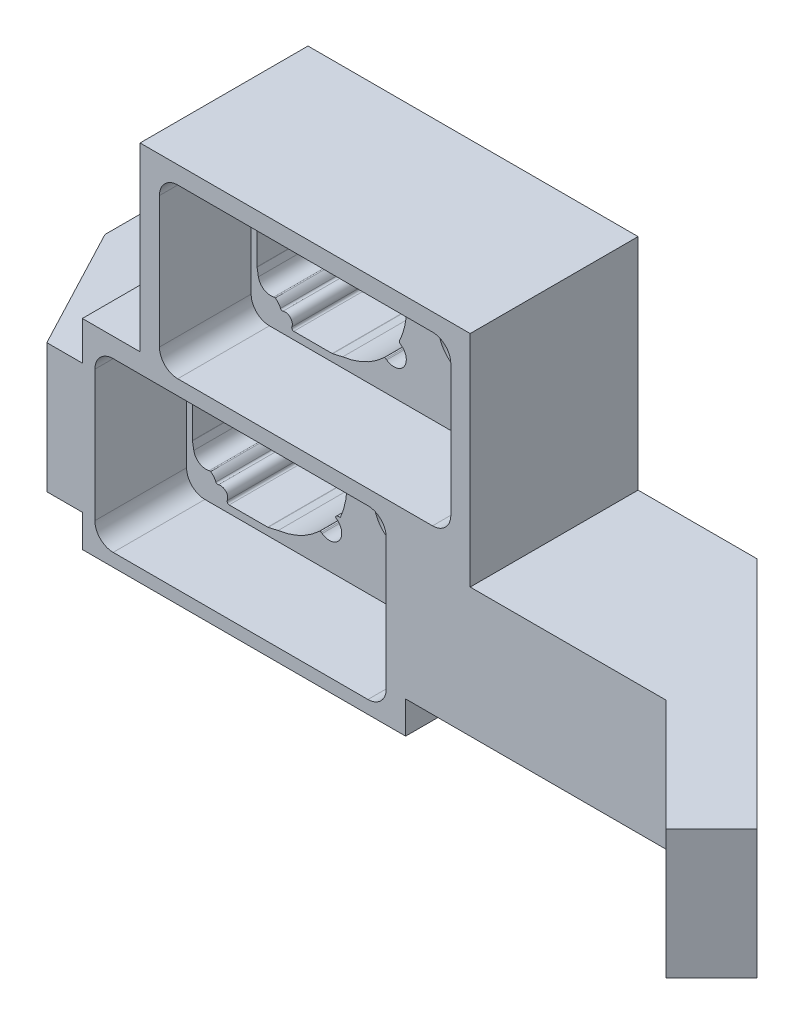
SolidWorks part; units mm, degrees
note: The reader was unsure of these and kept them because the rebuilt part matched: shared geometry of "Sketch5<3>", "Sketch5<4>".
ref_plane "Front Plane" through (0, 0, 0) normal (0, 0, 1) x (1, 0, 0)
ref_plane "Top Plane" through (0, 0, 0) normal (0, 1, 0) x (1, 0, 0)
ref_plane "Right Plane" through (0, 0, 0) normal (1, 0, 0) x (0, 0, -1)
sketch "Sketch2" plane through (0, 0, 0) normal (0, 1, 0) x (1, 0, 0)
  line L0 (0, 0) -> (269.0165, 0)
  line L1 (0, 0) -> (-341.2497, -341.2497)
  line L2 (0, 0) -> (341.2497, -341.2497)
  line L3 (341.2497, -341.2497) -> (0, -682.4995)
  line L4 (-341.2497, -341.2497) -> (0, -682.4995)
  line L5 (-8.9803, -8.9803) -> (332.2695, -350.23)
  line L6 (-41.275, -60.96) -> (41.275, -60.96)
  line L7 (-41.275, -60.96) -> (-41.275, -86.36)
  line L8 (-41.275, -86.36) -> (41.275, -86.36)
  line L9 (41.275, -60.96) -> (41.275, -86.36)
  line L10 (-41.275, -60.96) -> (41.275, -86.36) construction
  line L11 (-41.275, -86.36) -> (41.275, -60.96) construction
  line L12 (35.3795, -53.34) -> (-12.7, -53.34)
  line L13 (-12.7, -53.34) -> (-12.7, -40.64)
  line L14 (-12.7, -40.64) -> (40.64, -40.64)
  line L15 (43.18, -61.1405) -> (43.18, -87.63)
  line L16 (43.18, -87.63) -> (16.51, -87.63)
  line L17 (16.51, -87.63) -> (16.51, -90.17)
  line L18 (16.51, -90.17) -> (90.17, -90.17)
  line L19 (45.72, -90.17) -> (45.72, -106.68)
  line L20 (6.35, -90.424) -> (44.45, -90.424)
  line L21 (6.35, -90.424) -> (6.35, -100.076)
  line L22 (6.35, -100.076) -> (44.45, -100.076)
  line L23 (44.45, -90.424) -> (44.45, -100.076)
  line L24 (6.35, -90.424) -> (44.45, -100.076) construction
  line L25 (6.35, -100.076) -> (44.45, -90.424) construction
  line L26 (-6.35, -88.9) -> (6.35, -88.9)
  line L27 (-6.35, -88.9) -> (-6.35, -101.6)
  line L28 (-6.35, -101.6) -> (6.35, -101.6)
  line L29 (6.35, -88.9) -> (6.35, -101.6)
  line L30 (-6.35, -88.9) -> (6.35, -101.6) construction
  line L31 (-6.35, -101.6) -> (6.35, -88.9) construction
  line L32 (45.72, -106.68) -> (106.68, -106.68)
  line L33 (6.985, -107.95) -> (-12.7, -107.95)
  line L34 (-12.7, -139.7) -> (121.7395, -139.7)
  line L35 (6.985, -107.95) -> (6.985, -106.68)
  line L36 (6.985, -106.68) -> (45.72, -106.68)
  line L37 (-12.7, -107.95) -> (-12.7, -139.7)
  line L38 (12.7, -53.34) -> (12.7, -59.055)
  line L39 (121.7395, -139.7) -> (143.6841, -161.6446)
  line L40 (143.6841, -161.6446) -> (152.6644, -152.6644)
  line L41 (12.7, -59.055) -> (41.0945, -59.055)
  line L42 (-12.7, -115.57) -> (0, -139.7)
  line L43 (6.985, -106.68) -> (-12.7, -107.95)
  point P5 (0, -73.66)
  point P19 (25.4, -95.25)
  point P27 (0, -95.25)
  point P33 (16.51, -88.9)
  point P48 (88.7195, -106.68)
  dimension "D1" = 482.6
  dimension "D2" = 482.6
  dimension "D3" = 45
  dimension "D4" = 25.4
  dimension "D5" = 82.55
  dimension "D6" = 73.66
  dimension "D7" = 12.7
  dimension "D8" = 12.7
  dimension "D9" = 7.62
  dimension "D10" = 1.905
  dimension "D11" = 1.27
  dimension "D12" = 2.54
  dimension "D13" = 12.7
  dimension "D14" = 12.7
  dimension "D15" = 12.7
  dimension "D16" = 9.652
  dimension "D17" = 9.906
  dimension "D18" = 38.1
  dimension "D19" = 21.59
  dimension "D20" = 25.4
  dimension "D21" = 8.89
  dimension "D22" = 1.27
  dimension "D23" = 16.51
  dimension "D24" = 1.27
  dimension "D25" = 0.635
  dimension "D26" = 12.7
  dimension "D27" = 31.75
  dimension "D28" = 215.9
  dimension "D29" = 1.905
  dimension "D30" = 12.7
  dimension "D31" = 7.62
  dimension "D32" = 12.7
extrude "Boss-Extrude1" add sketch "Sketch2" along normal blind 25.4 contours L37 L42 L34 L5 L32 L36 L35 L33 | L5 L40 L2 L32 | L35 L43 L33
ref_plane "Plane1" through (0, 0, 106.68) normal (0, 0, -1) x (-1, 0, 0)
sketch "Sketch3" plane through (0, 0, 106.68) normal (0, 0, -1) x (-1, 0, 0)
  line L1 (-6.985, 0) -> (12.7, 0) construction
  line L2 (12.7, 25.4) -> (12.7, 0) construction
  circle A0 centre (0, 12.7) radius 11.1125
  dimension "D1" = 22.225
  dimension "D2" = 12.7
  dimension "D3" = 12.7
sketch "Sketch5" plane through (0, 0, 106.68) normal (0, 0, -1) x (-1, 0, 0)
  line L0 (-66.75, 25.6) -> (-66.75, -0.2)
  line L1 (-63.15, -3.8) -> (-13.05, -3.8)
  line L2 (-9.45, -0.2) -> (-9.45, 25.6)
  line L3 (-13.05, 29.2) -> (-63.15, 29.2)
  line L4 (-10.6112, 20.4467) -> (-10.8742, 21.9383)
  line L5 (-10.6051, 5.0227) -> (-10.6051, 20.3773)
  line L6 (-10.8742, 3.4617) -> (-10.6112, 4.9533)
  line L7 (-25.3918, -2.3449) -> (-17.8279, -2.3449)
  line L8 (-27.4594, -1.8827) -> (-25.4809, -2.3348)
  line L9 (-36.1085, 1.9194) -> (-35.9287, 2.05)
  line L10 (-38.7, 6.0374) -> (-38.9621, 5.847)
  line L11 (-38.9621, 19.553) -> (-38.7, 19.3626)
  line L12 (-35.9287, 23.35) -> (-36.1085, 23.4806)
  line L13 (-25.4809, 27.7348) -> (-27.4594, 27.2827)
  line L14 (-17.8279, 27.7449) -> (-25.3918, 27.7449)
  line L15 (-6.985, 0) -> (-106.68, 0) construction
  line L16 (-79.45, 61.521) -> (-79.45, 35.721)
  line L17 (-75.85, 32.121) -> (-25.75, 32.121)
  line L18 (-22.15, 35.721) -> (-22.15, 61.521)
  line L19 (-25.75, 65.121) -> (-75.85, 65.121)
  line L20 (-23.3112, 56.3678) -> (-23.5742, 57.8593)
  line L21 (-23.3051, 40.9437) -> (-23.3051, 56.2983)
  line L22 (-23.5742, 39.3827) -> (-23.3112, 40.8743)
  line L23 (-38.0918, 33.5761) -> (-30.5279, 33.5761)
  line L24 (-40.1594, 34.0383) -> (-38.1809, 33.5862)
  line L25 (-48.8085, 37.8404) -> (-48.6287, 37.971)
  line L26 (-51.4, 41.9584) -> (-51.6621, 41.7681)
  line L27 (-51.6621, 55.474) -> (-51.4, 55.2836)
  line L28 (-48.6287, 59.271) -> (-48.8085, 59.4016)
  line L29 (-38.1809, 63.6558) -> (-40.1594, 63.2037)
  line L30 (-30.5279, 63.6659) -> (-38.0918, 63.6659)
  arc A0 (-49.3655, 16.5858) -> (-49.3655, 8.8142) centre (-50.8, 12.7) ccw
  arc A1 (-63.15, 29.2) -> (-66.75, 25.6) centre (-63.15, 25.6) ccw
  arc A2 (-66.75, -0.2) -> (-63.15, -3.8) centre (-63.15, -0.2) ccw
  arc A3 (-13.05, -3.8) -> (-9.45, -0.2) centre (-13.05, -0.2) ccw
  arc A4 (-9.45, 25.6) -> (-13.05, 29.2) centre (-13.05, 25.6) ccw
  circle A5 centre (-52.4, 12.7) radius 6.114
  arc A6 (-15.2144, 25.1458) -> (-14.1814, 23.8887) centre (-12.65, 26.2) ccw
  arc A7 (-10.8742, 21.9383) -> (-13.9331, 23.8504) centre (-13.2647, 21.5168) ccw
  arc A8 (-10.6051, 20.3773) -> (-10.6112, 20.4467) centre (-11.0051, 20.3773) ccw
  arc A9 (-10.6112, 4.9533) -> (-10.6051, 5.0227) centre (-11.0051, 5.0227) ccw
  arc A10 (-13.9331, 1.5496) -> (-10.8742, 3.4617) centre (-13.2647, 3.8832) ccw
  arc A11 (-14.1814, 1.5113) -> (-15.2144, 0.2542) centre (-12.65, -0.8) ccw
  arc A12 (-15.7102, 0.0266) -> (-17.4545, -1.8014) centre (-16.15, -1.3) ccw
  arc A13 (-25.4809, -2.3348) -> (-25.3918, -2.3449) centre (-25.3918, -1.9449) ccw
  arc A14 (-35.5457, 2.0247) -> (-27.4594, -1.8827) centre (-25.4, 12.7) ccw
  arc A15 (-38.9621, 5.847) -> (-36.1085, 1.9194) centre (-37.5353, 3.8832) ccw
  arc A16 (-39.6713, 18.9909) -> (-39.6713, 6.4091) centre (-25.4, 12.7) ccw
  arc A17 (-36.1085, 23.4806) -> (-38.9621, 19.553) centre (-37.5353, 21.5168) ccw
  arc A18 (-27.4594, 27.2827) -> (-35.5457, 23.3753) centre (-25.4, 12.7) ccw
  arc A19 (-25.3918, 27.7449) -> (-25.4809, 27.7348) centre (-25.3918, 27.3449) ccw
  arc A20 (-17.4545, 27.2014) -> (-15.7102, 25.3734) centre (-16.15, 26.7) ccw
  arc A21 (-62.0655, 52.5068) -> (-62.0655, 44.7352) centre (-63.5, 48.621) ccw
  arc A22 (-75.85, 65.121) -> (-79.45, 61.521) centre (-75.85, 61.521) ccw
  arc A23 (-79.45, 35.721) -> (-75.85, 32.121) centre (-75.85, 35.721) ccw
  arc A24 (-25.75, 32.121) -> (-22.15, 35.721) centre (-25.75, 35.721) ccw
  arc A25 (-22.15, 61.521) -> (-25.75, 65.121) centre (-25.75, 61.521) ccw
  circle A26 centre (-65.1, 48.621) radius 6.114
  arc A27 (-27.9144, 61.0669) -> (-26.8814, 59.8097) centre (-25.35, 62.121) ccw
  arc A28 (-23.5742, 57.8593) -> (-26.6331, 59.7714) centre (-25.9647, 57.4378) ccw
  arc A29 (-23.3051, 56.2983) -> (-23.3112, 56.3678) centre (-23.7051, 56.2983) ccw
  arc A30 (-23.3112, 40.8743) -> (-23.3051, 40.9437) centre (-23.7051, 40.9437) ccw
  arc A31 (-26.6331, 37.4706) -> (-23.5742, 39.3827) centre (-25.9647, 39.8042) ccw
  arc A32 (-26.8814, 37.4323) -> (-27.9144, 36.1752) centre (-25.35, 35.121) ccw
  arc A33 (-28.4102, 35.9476) -> (-30.1545, 34.1196) centre (-28.85, 34.621) ccw
  arc A34 (-38.1809, 33.5862) -> (-38.0918, 33.5761) centre (-38.0918, 33.9761) ccw
  arc A35 (-48.2457, 37.9458) -> (-40.1594, 34.0383) centre (-38.1, 48.621) ccw
  arc A36 (-51.6621, 41.7681) -> (-48.8085, 37.8404) centre (-50.2353, 39.8042) ccw
  arc A37 (-51.3055, 54.9119) -> (-51.3055, 42.3301) centre (-38.1, 48.621) ccw
  arc A38 (-48.8085, 59.4016) -> (-51.6621, 55.474) centre (-50.2353, 57.4378) ccw
  arc A39 (-40.1594, 63.2037) -> (-48.2457, 59.2963) centre (-38.1, 48.621) ccw
  arc A40 (-38.0918, 63.6659) -> (-38.1809, 63.6558) centre (-38.0918, 63.2659) ccw
  arc A41 (-30.1545, 63.1224) -> (-28.4102, 61.2945) centre (-28.85, 62.621) ccw
  spline S0 degree 3 poles (-47.782, 15.5405) (-47.8302, 15.5901) (-47.9247, 15.6873) (-48.0726, 15.8214) (-48.22, 15.9439) (-48.3667, 16.0548) (-48.5567, 16.1861) (-48.7933, 16.3285) (-49.0779, 16.4727) (-49.2712, 16.5487) (-49.3655, 16.5858) knots 0 0 0 0 0.10878 0.213334 0.313673 0.409805 0.501742 0.675683 0.841732 1 1 1 1
  spline S1 degree 3 poles (-49.3655, 8.8142) (-49.309, 8.8358) (-49.1943, 8.8798) (-49.0238, 8.9564) (-48.852, 9.0425) (-48.6797, 9.1393) (-48.4829, 9.2626) (-48.2613, 9.4212) (-48.0157, 9.6236) (-47.8616, 9.7791) (-47.782, 9.8595) knots 0 0 0 0 0.094499 0.191816 0.291979 0.395011 0.500935 0.655694 0.822034 1 1 1 1
  spline S2 degree 3 poles (-47.782, 9.8595) (-47.736, 9.9095) (-47.6428, 10.011) (-47.5105, 10.1747) (-47.3824, 10.3498) (-47.2604, 10.5371) (-47.1455, 10.7366) (-47.039, 10.9482) (-46.9218, 11.2193) (-46.8086, 11.5494) (-46.7176, 11.9356) (-46.6623, 12.3193) (-46.6555, 12.5742) (-46.6522, 12.7) knots 0 0 0 0 0.065343 0.132731 0.202172 0.273671 0.347234 0.422865 0.500569 0.630039 0.756419 0.879731 1 1 1 1
  spline S3 degree 3 poles (-46.6522, 12.7) (-46.653, 12.7626) (-46.6547, 12.8885) (-46.6682, 13.0783) (-46.6901, 13.2695) (-46.7215, 13.4619) (-46.7624, 13.6549) (-46.8131, 13.848) (-46.8738, 14.0407) (-46.9696, 14.2994) (-47.1124, 14.611) (-47.3155, 14.957) (-47.5368, 15.2676) (-47.7017, 15.4512) (-47.782, 15.5405) knots 0 0 0 0 0.05983 0.12042 0.181774 0.243895 0.306785 0.370449 0.434888 0.500106 0.634538 0.762645 0.884456 1 1 1 1
  spline S4 degree 3 poles (-15.2144, 25.1458) (-15.2527, 25.2392) (-15.3267, 25.3157) (-15.5084, 25.399) (-15.6144, 25.4052) (-15.7102, 25.3734) knots 0 0 0 0 0.000302 0.000302 0.000604 0.000604 0.000604 0.000604 weights 1 1 1 1 1 1
  spline S5 degree 3 poles (-13.9331, 23.8504) (-14.0168, 23.8264) (-14.1087, 23.8406) (-14.1814, 23.8887) knots 0 0 0 0 0.000258 0.000258 0.000258 0.000258 weights 1 1 1 1
  spline S6 degree 3 poles (-14.1814, 1.5113) (-14.1087, 1.5594) (-14.0168, 1.5736) (-13.9331, 1.5496) knots 0 0 0 0 0.000258 0.000258 0.000258 0.000258 weights 1 1 1 1
  spline S7 degree 3 poles (-15.7102, 0.0266) (-15.6144, -0.0052) (-15.5082, 0.001) (-15.3265, 0.0845) (-15.2527, 0.1608) (-15.2144, 0.2542) knots 0 0 0 0 0.000302 0.000302 0.000604 0.000604 0.000604 0.000604 weights 1 1 1 1 1 1
  spline S8 degree 3 poles (-17.8279, -2.3449) (-17.6976, -2.3449) (-17.5713, -2.2779) (-17.4248, -2.0643) (-17.4078, -1.9231) (-17.4545, -1.8014) knots 0 0 0 0 0.000388 0.000388 0.000776 0.000776 0.000776 0.000776 weights 1 1 1 1 1 1
  spline S9 degree 3 poles (-35.9287, 2.05) (-35.872, 2.0912) (-35.8026, 2.1112) (-35.6631, 2.1021) (-35.5966, 2.073) (-35.5457, 2.0247) knots 0 0 0 0 0.000207 0.000207 0.000415 0.000415 0.000415 0.000415 weights 1 1 1 1 1 1
  spline S10 degree 3 poles (-39.6713, 6.4091) (-39.4915, 6.4703) (-39.2959, 6.4665) (-38.942, 6.3313) (-38.7931, 6.203) (-38.7, 6.0374) knots 0 0 0 0 0.000207 0.000207 0.000414 0.000414 0.000414 0.000414 weights 1 1 1 1 1 1
  spline S11 degree 3 poles (-38.7, 19.3626) (-38.7931, 19.197) (-38.9412, 19.0692) (-39.2949, 18.9336) (-39.4915, 18.9297) (-39.6713, 18.9909) knots 0 0 0 0 0.000207 0.000207 0.000414 0.000414 0.000414 0.000414 weights 1 1 1 1 1 1
  spline S12 degree 3 poles (-35.5457, 23.3753) (-35.5966, 23.327) (-35.6627, 23.298) (-35.8022, 23.2887) (-35.872, 23.3088) (-35.9287, 23.35) knots 0 0 0 0 0.000207 0.000207 0.000415 0.000415 0.000415 0.000415 weights 1 1 1 1 1 1
  spline S13 degree 3 poles (-17.4545, 27.2014) (-17.4078, 27.3231) (-17.425, 27.465) (-17.5718, 27.6783) (-17.6976, 27.7449) (-17.8279, 27.7449) knots 0 0 0 0 0.000388 0.000388 0.000776 0.000776 0.000776 0.000776 weights 1 1 1 1 1 1
  spline S14 degree 3 poles (-60.482, 51.4615) (-60.5302, 51.5111) (-60.6247, 51.6083) (-60.7726, 51.7424) (-60.92, 51.865) (-61.0667, 51.9758) (-61.2567, 52.1071) (-61.4933, 52.2495) (-61.7779, 52.3937) (-61.9712, 52.4697) (-62.0655, 52.5068) knots 0 0 0 0 0.10878 0.213334 0.313673 0.409805 0.501742 0.675683 0.841732 1 1 1 1
  spline S15 degree 3 poles (-62.0655, 44.7352) (-62.009, 44.7569) (-61.8943, 44.8008) (-61.7238, 44.8774) (-61.552, 44.9635) (-61.3797, 45.0603) (-61.1829, 45.1836) (-60.9613, 45.3422) (-60.7157, 45.5446) (-60.5616, 45.7001) (-60.482, 45.7805) knots 0 0 0 0 0.094499 0.191816 0.291979 0.395011 0.500935 0.655694 0.822034 1 1 1 1
  spline S16 degree 3 poles (-60.482, 45.7805) (-60.436, 45.8305) (-60.3428, 45.932) (-60.2105, 46.0957) (-60.0824, 46.2708) (-59.9604, 46.4582) (-59.8455, 46.6576) (-59.739, 46.8692) (-59.6218, 47.1403) (-59.5086, 47.4705) (-59.4176, 47.8566) (-59.3623, 48.2403) (-59.3555, 48.4952) (-59.3522, 48.621) knots 0 0 0 0 0.065343 0.132731 0.202172 0.273671 0.347234 0.422865 0.500569 0.630039 0.756419 0.879731 1 1 1 1
  spline S17 degree 3 poles (-59.3522, 48.621) (-59.353, 48.6836) (-59.3547, 48.8096) (-59.3682, 48.9993) (-59.3901, 49.1906) (-59.4215, 49.383) (-59.4624, 49.576) (-59.5131, 49.7691) (-59.5738, 49.9618) (-59.6696, 50.2204) (-59.8124, 50.5321) (-60.0155, 50.878) (-60.2368, 51.1887) (-60.4017, 51.3722) (-60.482, 51.4615) knots 0 0 0 0 0.05983 0.12042 0.181774 0.243895 0.306785 0.370449 0.434888 0.500106 0.634538 0.762645 0.884456 1 1 1 1
  spline S18 degree 3 poles (-27.9144, 61.0669) (-27.9527, 61.1602) (-28.0267, 61.2367) (-28.2084, 61.32) (-28.3144, 61.3262) (-28.4102, 61.2945) knots 0 0 0 0 0.000302 0.000302 0.000604 0.000604 0.000604 0.000604 weights 1 1 1 1 1 1
  spline S19 degree 3 poles (-26.6331, 59.7714) (-26.7168, 59.7474) (-26.8087, 59.7616) (-26.8814, 59.8097) knots 0 0 0 0 0.000258 0.000258 0.000258 0.000258 weights 1 1 1 1
  spline S20 degree 3 poles (-26.8814, 37.4323) (-26.8087, 37.4804) (-26.7168, 37.4946) (-26.6331, 37.4706) knots 0 0 0 0 0.000258 0.000258 0.000258 0.000258 weights 1 1 1 1
  spline S21 degree 3 poles (-28.4102, 35.9476) (-28.3144, 35.9158) (-28.2082, 35.9221) (-28.0265, 36.0055) (-27.9527, 36.0818) (-27.9144, 36.1752) knots 0 0 0 0 0.000302 0.000302 0.000604 0.000604 0.000604 0.000604 weights 1 1 1 1 1 1
  spline S22 degree 3 poles (-30.5279, 33.5761) (-30.3976, 33.5761) (-30.2713, 33.6431) (-30.1248, 33.8567) (-30.1078, 33.998) (-30.1545, 34.1196) knots 0 0 0 0 0.000388 0.000388 0.000776 0.000776 0.000776 0.000776 weights 1 1 1 1 1 1
  spline S23 degree 3 poles (-48.6287, 37.971) (-48.572, 38.0122) (-48.5026, 38.0322) (-48.3631, 38.0231) (-48.2966, 37.9941) (-48.2457, 37.9458) knots 0 0 0 0 0.000207 0.000207 0.000415 0.000415 0.000415 0.000415 weights 1 1 1 1 1 1
  spline S24 degree 3 poles (-51.3055, 42.3301) (-51.2754, 42.2669) (-51.2684, 42.1951) (-51.3028, 42.0597) (-51.3434, 41.9996) (-51.4, 41.9584) knots 0 0 0 0 0.000207 0.000207 0.000414 0.000414 0.000414 0.000414 weights 1 1 1 1 1 1
  spline S25 degree 3 poles (-51.4, 55.2836) (-51.3434, 55.2424) (-51.3029, 55.1827) (-51.2684, 55.0473) (-51.2754, 54.9751) (-51.3055, 54.9119) knots 0 0 0 0 0.000207 0.000207 0.000414 0.000414 0.000414 0.000414 weights 1 1 1 1 1 1
  spline S26 degree 3 poles (-48.2457, 59.2963) (-48.2966, 59.248) (-48.3627, 59.219) (-48.5022, 59.2098) (-48.572, 59.2298) (-48.6287, 59.271) knots 0 0 0 0 0.000207 0.000207 0.000415 0.000415 0.000415 0.000415 weights 1 1 1 1 1 1
  spline S27 degree 3 poles (-30.1545, 63.1224) (-30.1078, 63.2441) (-30.125, 63.386) (-30.2718, 63.5994) (-30.3976, 63.6659) (-30.5279, 63.6659) knots 0 0 0 0 0.000388 0.000388 0.000776 0.000776 0.000776 0.000776 weights 1 1 1 1 1 1
  dimension "D1" = 1.6
  dimension "D2" = 25.4
  dimension "D3" = 15.95
  dimension "D4" = 16.5
  dimension "D5" = 12.7
  dimension "D6" = 1.6
  dimension "D7" = 25.4
  dimension "D8" = 15.95
  dimension "D9" = 16.5
  dimension "D10" = 38.1
  dimension "D11" = 12.7
sketch "Sketch6" plane through (0, 0, 0) normal (0, -1, 0) x (1, 0, 0)
  line L0 (0, 139.7) -> (121.7395, 139.7) construction
  line L1 (6.985, 106.68) -> (106.68, 106.68)
  line L2 (6.985, 106.68) -> (6.985, 139.7)
  line L3 (6.985, 139.7) -> (106.68, 139.7)
  line L4 (106.68, 106.68) -> (106.68, 139.7)
  point P7 (0, 0)
extrude "Boss-Extrude2" add sketch "Sketch6" along normal blind 6.35 and the other way offset from surface (68.58 mm away) 43.18 contours L2 L3 L4 L1 other way up to face at (63.2941, 25.4, 128.8236)
extrude "Cut-Extrude2" cut sketch "Sketch5" along normal blind 18.034 from surface at -33.02 contours L19 A22 L16 A23 L17 A24 L18 A25 | L3 A1 L0 A2 L1 A3 L2 A4 starting at face at (58.1782, 18.8383, 139.7)
extrude "Cut-Extrude3" cut sketch "Sketch3" against normal blind 7.1628
extrude "Cut-Extrude4" cut sketch "Sketch5<3>" against normal up to next contours A20 S13 L14 A19 L13 A18 S12 L12 A17 L11 S11 A16 S10 L10 A15 L9 S9 A14 L8 A13 L7 S8 A12 S7 A11 S6 A10 L6 A9 L5 A8 L4 A7 S5 A6 S4 | S16 S17 S14 A21 S15 | A41 S27 L30 A40 L29 A39 S26 L28 A38 L27 S25 A37 S24 L26 A36 L25 S23 A35 L24 A34 L23 S22 A33 S21 A32 S20 A31 L22 A30 L21 A29 L20 A28 S19 A27 S18 | A0 S1 S2 S3 S0
sketch "Sketch5<3>" plane through (0, 0, 106.68) normal (0, 0, -1) x (-1, 0, 0) same geometry as "Sketch5"
extrude "Cut-Extrude5" cut sketch "Sketch5<4>" along normal blind 2.54 from surface at -14.986 contours A5 S3 S2 S1 A0 S0 | A26 starting at face at (50.8, 48.621, 121.666)
sketch "Sketch5<4>" plane through (0, 0, 106.68) normal (0, 0, -1) x (-1, 0, 0) same geometry as "Sketch5"
sketch "Sketch7" plane through (0, 0, 106.68) normal (0, 0, -1) x (-1, 0, 0)
  line L0 (-6.985, 21.3428) -> (-10.6051, 20.3773)
  line L1 (-6.985, 4.0572) -> (-10.6112, 4.9533)
  line L3 (-10.6051, 20.3773) -> (-10.6051, 16.0195)
  line L4 (-10.6051, 16.0195) -> (-6.985, 21.3428)
  line L5 (-10.6112, 4.9533) -> (-10.6051, 9.3805)
  line L6 (-10.6051, 9.3805) -> (-6.985, 4.0572)
  arc A0 (-10.6051, 9.3805) -> (-6.985, 4.0572) centre (0, 12.7) ccw construction
  arc A1 (-6.985, 21.3428) -> (-10.6051, 16.0195) centre (0, 12.7) ccw construction
extrude "Cut-Extrude6" cut sketch "Sketch7" against normal up to surface (7.1628 mm away) up to face at (-0.2537, 12.7, 113.8428)
ref_plane "Plane2" through (0, 0, 106.68) normal (0, 0, -1) x (-1, 0, 0)
sketch "Sketch8" plane through (0, 0, 106.68) normal (0, 0, -1) x (-1, 0, 0)
  line L0 (-83.26, 68.58) -> (-83.26, 25.4)
  line L1 (-6.985, 68.58) -> (-106.68, 68.58) construction
  line L2 (-106.68, 25.4) -> (-83.26, 25.4)
  line L3 (-79.45, 61.521) -> (-79.45, 35.721) construction
  line L4 (-18.34, 68.58) -> (-18.34, 33.01)
  line L8 (-106.68, 0) -> (-70.56, 0)
  line L9 (-70.56, 0) -> (-70.56, -6.35)
  line L10 (-6.985, -6.35) -> (-106.68, -6.35) construction
  line L11 (-66.75, 25.6) -> (-66.75, -0.2) construction
  line L12 (-18.34, 33.01) -> (-6.985, 33.01)
  line L14 (-22.15, 35.721) -> (-22.15, 61.521) construction
  line L15 (-13.05, 29.2) -> (-63.15, 29.2) construction
  line L16 (-106.68, 0) -> (-106.68, -6.35)
  line L17 (-106.68, -6.35) -> (-70.56, -6.35)
  line L18 (-106.68, 25.4) -> (-106.68, 68.58)
  line L19 (-106.68, 68.58) -> (-83.26, 68.58)
  line L22 (-18.34, 68.58) -> (-6.985, 68.58)
  line L23 (-6.985, 68.58) -> (-6.985, 33.01)
  dimension "D1" = 3.81
  dimension "D2" = 90
  dimension "D3" = 3.81
  dimension "D4" = 3.81
  dimension "D5" = 3.81
extrude "Cut-Extrude7" cut sketch "Sketch8" against normal up to next
